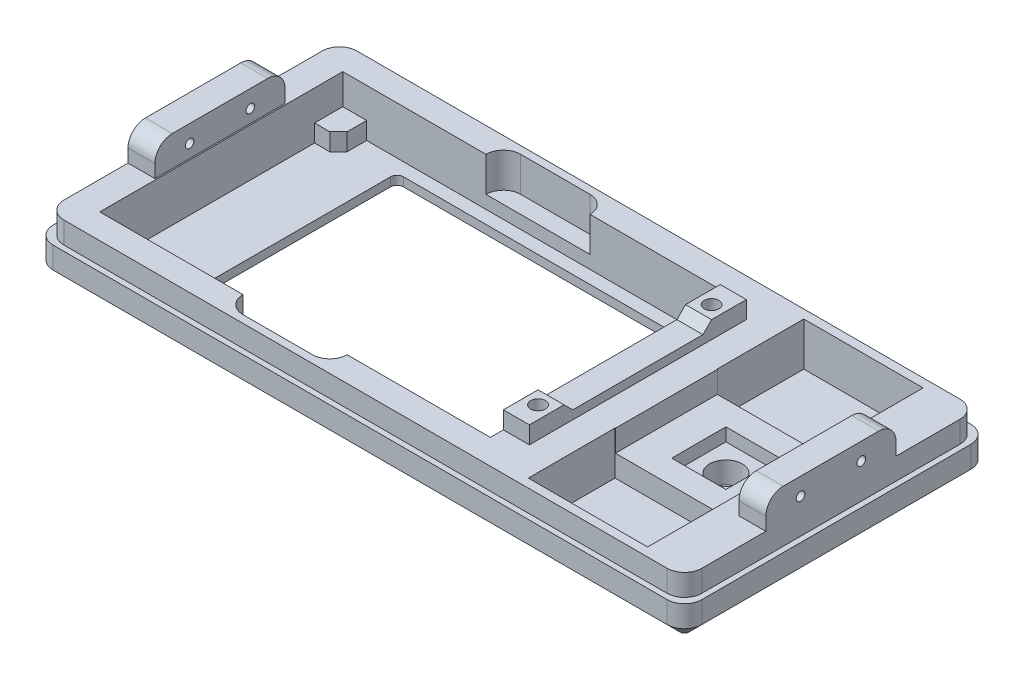
SolidWorks part; units mm, degrees
ref_plane "Front Plane" through (0, 0, 0) normal (0, 0, 1) x (1, 0, 0)
ref_plane "Top Plane" through (0, 0, 0) normal (0, 1, 0) x (1, 0, 0)
ref_plane "Right Plane" through (0, 0, 0) normal (1, 0, 0) x (0, 0, -1)
sketch "Sketch1" plane through (0, 0, 0) normal (0, 1, 0) x (1, 0, 0)
  line L1 (-74.75, 35) -> (74.75, 35)
  line L2 (-74.75, 35) -> (-74.75, -35)
  line L3 (-74.75, -35) -> (74.75, -35)
  line L4 (74.75, 35) -> (74.75, -35)
  line L5 (-74.75, 35) -> (74.75, -35) construction
  line L6 (-74.75, -35) -> (74.75, 35) construction
  point P0 (0, 0)
  dimension "D1" = 70
  dimension "D2" = 149.5
extrude "Boss-Extrude1" add sketch "Sketch1" along normal blind 8
fillet "Fillet1" radius 4 4 edges at (-74.75, 4, -35) (-74.75, 4, 35) (74.75, 4, -35) (74.75, 4, 35)
sketch "Sketch6" plane through (0, 8, 0) normal (0, 1, 0) x (1, 0, 0)
  line L1 (-73.5, 33.75) -> (73.5, 33.75)
  line L2 (-73.5, 33.75) -> (-73.5, -33.75)
  line L3 (-73.5, -33.75) -> (73.5, -33.75)
  line L4 (73.5, 33.75) -> (73.5, -33.75)
  line L5 (-73.5, 33.75) -> (73.5, -33.75) construction
  line L6 (-73.5, -33.75) -> (73.5, 33.75) construction
  point P0 (0, 0)
  dimension "D1" = 67.5
  dimension "D2" = 147
extrude "Boss-Extrude3" add sketch "Sketch6" along normal blind 5
fillet "Fillet2" radius 4 4 edges at (-73.5, 10.5, 33.75) (73.5, 10.5, 33.75) (73.5, 10.5, -33.75) (-73.5, 10.5, -33.75)
sketch "Sketch7" plane through (0, 13, 0) normal (0, 1, 0) x (1, 0, 0)
  line L0 (-73.5, 0) -> (0, 0) construction
  line L1 (-73.5, 29.75) -> (-73.5, -29.75) construction
  line L2 (0, 0) -> (0, 33.75) construction
  line L3 (69.5, 33.75) -> (-69.5, 33.75) construction
  line L4 (-73.5, -15) -> (-73.5, 15)
  line L5 (-73.5, 29.75) -> (-73.5, -29.75) construction
  line L6 (-73.5, 15) -> (-67.2945, 15)
  line L7 (-67.2945, 15) -> (-67.2945, -15)
  line L8 (-73.5, -15) -> (-67.2945, -15)
  line L9 (73.5, 15) -> (67.2945, 15)
  line L10 (73.5, -15) -> (73.5, 15)
  line L11 (73.5, -15) -> (67.2945, -15)
  line L12 (67.2945, 15) -> (67.2945, -15)
  point P14 (-67.2945, 0)
  dimension "D1" = 15
extrude "Boss-Extrude4" add sketch "Sketch7" along normal blind 7
sketch "Sketch8" plane through (-73.5, 0, 0) normal (-1, 0, 0) x (0, 0, 1)
  line L0 (0, 20) -> (0, 0) construction
  line L1 (-15, 20) -> (15, 20) construction
  circle A0 centre (-7, 16) radius 1
  circle A1 centre (7, 16) radius 1
  dimension "D1" = 2
  dimension "D2" = 4
  dimension "D3" = 14
extrude "Cut-Extrude3" cut sketch "Sketch8" against normal through all
fillet "Fillet5" radius 4 4 edges at (70.3973, 20, 15) (70.3973, 20, -15) (-70.3973, 20, 15) (-70.3973, 20, -15)
sketch "Sketch9" plane through (0, 13, 0) normal (0, 1, 0) x (1, 0, 0)
  line L0 (0, 0) -> (-67.2945, 0) construction
  line L1 (-67.2945, -15) -> (-67.2945, 15) construction
  line L3 (-67, 28) -> (23, 28)
  line L4 (-67, 28) -> (-67, -28)
  line L5 (-67, -28) -> (23, -28)
  line L6 (23, 28) -> (23, -28)
  line L7 (-67, 28) -> (23, -28) construction
  line L8 (-67, -28) -> (23, 28) construction
  point P5 (-22, 0)
  dimension "D1" = 90
  dimension "D2" = 56
  dimension "D3" = 22
extrude "Cut-Extrude4" cut sketch "Sketch9" against normal blind 7
sketch "Sketch10" plane through (0, 6, 0) normal (0, 1, 0) x (1, 0, 0)
  line L0 (-67, 28) -> (23, -28) construction
  line L1 (23, 28) -> (-67, -28) construction
  line L3 (-61.5, 28) -> (17.5, 28)
  line L4 (-61.5, 28) -> (-61.5, -28)
  line L5 (-61.5, -28) -> (17.5, -28)
  line L6 (17.5, 28) -> (17.5, -28)
  line L7 (-61.5, 28) -> (17.5, -28) construction
  line L8 (-61.5, -28) -> (17.5, 28) construction
  point P8 (-22, 0)
  dimension "D1" = 79
  dimension "D2" = 56
extrude "Cut-Extrude5" cut sketch "Sketch10" against normal blind 4
sketch "Sketch11" plane through (0, 2, 0) normal (0, 1, 0) x (1, 0, 0)
  line L0 (-61.5, 0) -> (17.5, 0) construction
  line L1 (-61.5, 28) -> (-61.5, -28) construction
  line L2 (17.5, -28) -> (17.5, 28) construction
  line L4 (-51.5, 25) -> (14.5, 25)
  line L5 (-51.5, 25) -> (-51.5, -25)
  line L6 (-51.5, -25) -> (14.5, -25)
  line L7 (14.5, 25) -> (14.5, -25)
  line L8 (-51.5, 25) -> (14.5, -25) construction
  line L9 (-51.5, -25) -> (14.5, 25) construction
  point P6 (-18.5, 0)
  dimension "D1" = 66
  dimension "D2" = 50
  dimension "D3" = 3
extrude "Cut-Extrude6" cut sketch "Sketch11" against normal through all
sketch "Sketch13" plane through (0, 13, 0) normal (0, 1, 0) x (1, 0, 0)
  line L0 (23, 0) -> (67.2945, 0) construction
  line L1 (23, -28) -> (23, 28) construction
  line L2 (67.2945, 11) -> (67.2945, -11) construction
  line L3 (23, -25) -> (23, 25)
  line L4 (23, 25) -> (29, 25)
  line L5 (29, 25) -> (29, -25)
  line L6 (23, -25) -> (29, -25)
  point P10 (29, 0)
  dimension "D1" = 25
  dimension "D2" = 6
extrude "Boss-Extrude5" add sketch "Sketch13" along normal blind 4
sketch "Sketch14" plane through (0, 17, 0) normal (0, 1, 0) x (1, 0, 0)
  line L0 (23, 0) -> (29, 0) construction
  line L1 (23, 25) -> (23, -25) construction
  line L2 (29, -25) -> (29, 25) construction
  circle A0 centre (26, 20) radius 1.6928
  circle A1 centre (26, -20) radius 1.6928
  dimension "D1" = 3
  dimension "D2" = 20
extrude "Cut-Extrude7" cut sketch "Sketch14" against normal through all
sketch "Sketch15" plane through (0, 17, 0) normal (0, 1, 0) x (1, 0, 0)
  line L0 (23, 0) -> (29, 0) construction
  line L1 (23, 25) -> (23, -25) construction
  line L2 (29, -25) -> (29, 25) construction
  line L3 (23, -15) -> (23, 15)
  line L4 (23, -28) -> (23, 28) construction
  line L5 (23, 15) -> (29, 15)
  line L6 (29, -25) -> (29, 25) construction
  line L7 (29, 15) -> (29, -15)
  line L8 (23, -15) -> (29, -15)
  dimension "D1" = 15
extrude "Cut-Extrude8" cut sketch "Sketch15" against normal blind 2
chamfer "Chamfer2" distance 2 angle 45 2 edges at (26, 0, 18.3072) (26, 0, -18.3072)
sketch "Sketch16" plane through (0, 13, 0) normal (0, 1, 0) x (1, 0, 0)
  line L0 (0, 0) -> (67.2945, 0) construction
  line L1 (67.2945, 11) -> (67.2945, -11) construction
  circle A0 centre (49.2945, 0) radius 3.75
  dimension "D1" = 7.5
  dimension "D2" = 18
extrude "Cut-Extrude9" cut sketch "Sketch16" against normal through all
sketch "Sketch17" plane through (0, 13, 0) normal (0, 1, 0) x (1, 0, 0)
  line L1 (43.0445, 6.25) -> (55.5445, 6.25)
  line L2 (43.0445, 6.25) -> (43.0445, -6.25)
  line L3 (43.0445, -6.25) -> (55.5445, -6.25)
  line L4 (55.5445, 6.25) -> (55.5445, -6.25)
  line L5 (43.0445, 6.25) -> (55.5445, -6.25) construction
  line L6 (43.0445, -6.25) -> (55.5445, 6.25) construction
  point P0 (49.2945, 0)
  dimension "D1" = 12.5
  dimension "D2" = 12.5
extrude "Cut-Extrude10" cut sketch "Sketch17" against normal blind 8
sketch "Sketch20" plane through (0, 13, 0) normal (0, 1, 0) x (1, 0, 0)
  line L0 (-67.2945, 0) -> (67.2945, 0) construction
  line L1 (-67.2945, -11) -> (-67.2945, 11) construction
  line L2 (67.2945, 11) -> (67.2945, -11) construction
  line L3 (-22, 28) -> (-22, 33.75) construction
  line L4 (23, 28) -> (-67, 28) construction
  line L5 (69.5, 33.75) -> (-69.5, 33.75) construction
  line L6 (-10, 28) -> (-34, 28)
  line L7 (-34, 28) -> (-34, 32)
  line L8 (-34, 32) -> (-10, 32)
  line L9 (-10, 28) -> (-10, 32)
  line L10 (-10, -28) -> (-10, -32)
  line L11 (-34, -32) -> (-10, -32)
  line L12 (-34, -28) -> (-34, -32)
  line L13 (-10, -28) -> (-34, -28)
  point P17 (-22, 32)
  dimension "D1" = 12
  dimension "D2" = 4
extrude "Cut-Extrude12" cut sketch "Sketch20" against normal blind 8
fillet "Fillet6" radius 4 4 edges at (-34, 9, 32) (-10, 9, 32) (-10, 9, -32) (-34, 9, -32)
chamfer "Chamfer3" distance 2 angle 45 2 edges at (26, 17, 15) (26, 17, -15)
sketch "Sketch23" plane through (0, 6, 0) normal (0, 1, 0) x (1, 0, 0)
  line L0 (-61.5, 0) -> (-67, 0) construction
  line L1 (-61.5, 28) -> (-61.5, -28) construction
  line L2 (-67, 28) -> (-67, -28) construction
  line L3 (-61.5, -21.5) -> (-61.5, 21.5)
  line L4 (-61.5, 28) -> (-61.5, -28) construction
  line L5 (-61.5, 21.5) -> (-67, 21.5)
  line L6 (-67, 21.5) -> (-67, -21.5)
  line L7 (-61.5, -21.5) -> (-67, -21.5)
  line L8 (-22, -28) -> (-22, -10.1702) construction
  line L9 (-10, -28) -> (-34, -28) construction
  line L10 (17.5, 21.5) -> (23, 21.5)
  line L11 (17.5, -21.5) -> (17.5, 21.5)
  line L12 (17.5, -21.5) -> (23, -21.5)
  line L13 (23, 21.5) -> (23, -21.5)
  point P12 (-67, 0)
  dimension "D1" = 21.5
  dimension "D2" = 5.5
extrude "Cut-Extrude15" cut sketch "Sketch23" against normal blind 4
fillet "Fillet7" radius 1.5 4 edges at (14.5, 1, -25) (14.5, 1, 25) (-51.5, 1, 25) (-51.5, 1, -25)
chamfer "Chamfer6" distance 2 angle 45 4 edges at (-61.5, 4, 21.5) (-61.5, 4, -21.5) (17.5, 4, 21.5) (17.5, 4, -21.5)
sketch "Sketch26" plane through (0, 13, 0) normal (0, 1, 0) x (1, 0, 0)
  line L0 (-69.5, -33.75) -> (69.5, -33.75) construction
  line L1 (35.5, -11.75) -> (63, -11.75)
  line L2 (35.5, -11.75) -> (35.5, -31.75)
  line L3 (35.5, -31.75) -> (63, -31.75)
  line L4 (63, -11.75) -> (63, -31.75)
  line L5 (35.5, -11.75) -> (63, -31.75) construction
  line L6 (35.5, -31.75) -> (63, -11.75) construction
  line L7 (73.5, -29.75) -> (73.5, -15) construction
  line L8 (0, 0) -> (16.2431, 0) construction
  line L9 (35.5, 31.75) -> (63, 31.75)
  line L10 (63, 11.75) -> (63, 31.75)
  line L11 (35.5, 11.75) -> (63, 11.75)
  line L12 (35.5, 11.75) -> (35.5, 31.75)
  point P0 (49.25, -21.75)
  dimension "D1" = 20
  dimension "D2" = 27.5
  dimension "D3" = 12
  dimension "D4" = 10.5
extrude "Cut-Extrude16" cut sketch "Sketch26" against normal blind 10
sketch "Sketch27" plane through (0, 13, 0) normal (0, 1, 0) x (1, 0, 0)
  line L0 (63, -31.75) -> (63, -11.75) construction
  line L1 (35.5891, 14.4188) -> (63, 14.4188)
  line L2 (35.5891, 14.4188) -> (35.5891, -14.4188)
  line L3 (35.5891, -14.4188) -> (63, -14.4188)
  line L4 (63, 14.4188) -> (63, -14.4188)
  line L5 (35.5891, 14.4188) -> (63, -14.4188) construction
  line L6 (35.5891, -14.4188) -> (63, 14.4188) construction
  point P0 (49.2945, 0)
extrude "Cut-Extrude17" cut sketch "Sketch27" against normal blind 5
chamfer "Chamfer7" distance 3 angle 45 8 edges at (0, 0, 35) (73.5784, 0, 33.8284) (-73.5784, 0, 33.8284) (74.75, 0, 0) (-74.75, 0, 0) (73.5784, 0, -33.8284) (-73.5784, 0, -33.8284) (0, 0, -35)
